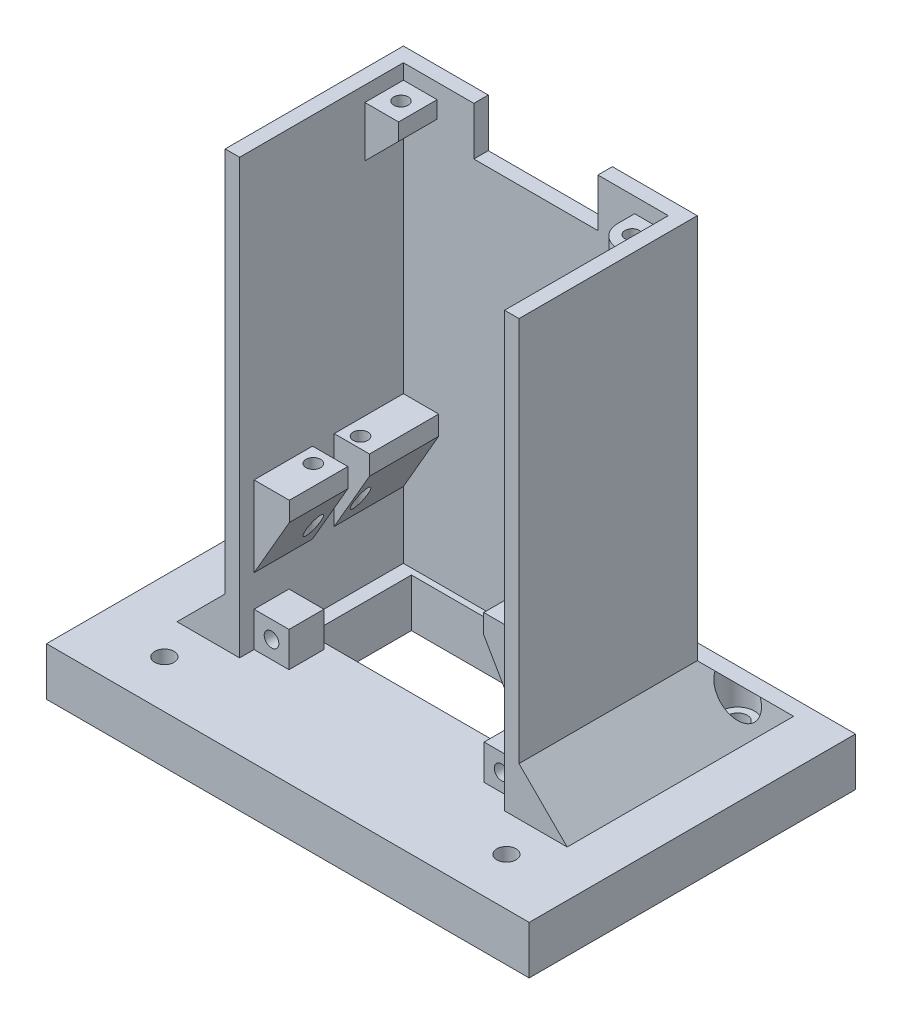
SolidWorks part; units mm, degrees
ref_plane "Front" through (0, 0, 0) normal (0, 0, 1) x (1, 0, 0)
ref_plane "Top" through (0, 0, 0) normal (0, 1, 0) x (1, 0, 0)
ref_plane "Right" through (0, 0, 0) normal (1, 0, 0) x (0, 0, -1)
sketch "Sketch1" plane through (0, 0, 0) normal (0, 0, 1) x (1, 0, 0)
  line L1 (0, 0) -> (55, 0)
  line L2 (0, 0) -> (0, 80)
  line L3 (0, 80) -> (55, 80)
  line L4 (55, 0) -> (55, 80)
  dimension "D1" = 55
  dimension "D2" = 80
extrude "BackPanel" add sketch "Sketch1" along normal blind 3
sketch "Sketch2" plane through (0, 0, 3) normal (0, 0, 1) x (1, 0, 0)
  line L0 (0, 80) -> (0, 0) construction
  line L1 (0, 16.5) -> (7.325, 16.5)
  line L2 (0, 16.5) -> (0, 20.5)
  line L3 (0, 20.5) -> (7.325, 20.5)
  line L4 (7.325, 16.5) -> (7.325, 20.5)
  line L5 (55, 0) -> (55, 80) construction
  line L6 (55, 16.5) -> (47.675, 16.5)
  line L7 (55, 16.5) -> (55, 20.5)
  line L8 (55, 20.5) -> (47.675, 20.5)
  line L9 (47.675, 16.5) -> (47.675, 20.5)
  line L10 (7.325, 16.5) -> (47.675, 16.5) construction
  line L11 (0, 0) -> (55, 0) construction
  dimension "D1" = 40.35
  dimension "D2" = 20.5
  dimension "D3" = 4
extrude "MotorMount" add sketch "Sketch2" along normal blind 34
sketch "Sketch3" plane through (0, 0, 0) normal (-1, 0, 0) x (0, 0, 1)
  line L0 (37, 20.5) -> (37, 16.5) construction
  line L1 (0, 0) -> (37, 0)
  line L2 (0, 0) -> (0, 80)
  line L3 (0, 80) -> (37, 80)
  line L4 (37, 0) -> (37, 80)
  line L5 (3, 80) -> (0, 80) construction
  point P7 (0, 80)
extrude "SidePanel2" add sketch "Sketch3" along normal blind 3
sketch "Sketch4" plane through (55, 0, 0) normal (1, 0, 0) x (0, 0, -1)
  line L0 (-37, 16.5) -> (-37, 20.5) construction
  line L1 (0, 80) -> (-37, 80)
  line L2 (0, 80) -> (0, 0)
  line L3 (0, 0) -> (-37, 0)
  line L4 (-37, 80) -> (-37, 0)
extrude "SidePanel1" add sketch "Sketch4" along normal blind 3
sketch "Sketch6" plane through (0, 0, 37) normal (0, 0, 1) x (1, 0, 0)
  line L0 (7.325, 16.5) -> (0, 3.8127)
  line L1 (0, 0) -> (0, 16.5) construction
  line L2 (0, 3.8127) -> (0, 16.5)
  line L3 (0, 16.5) -> (7.325, 16.5)
  line L4 (47.675, 16.5) -> (55, 16.5)
  line L5 (55, 16.5) -> (55, 3.8127)
  line L6 (55, 16.5) -> (55, 0) construction
  line L7 (55, 3.8127) -> (47.675, 16.5)
  line L8 (0, 16.5) -> (0, 0) construction
  dimension "D1" = 150
extrude "MotorSupportAngles" add sketch "Sketch6" against normal up to surface (34 mm away) up to face at (27.5, 25.6667, 3)
sketch "Sketch5" plane through (0, 20.5, 0) normal (0, 1, 0) x (1, 0, 0)
  line L0 (3.2, -3) -> (3.2, -15.1) construction
  line L2 (7.325, -3) -> (0, -3) construction
  line L3 (3.2, -24.9) -> (3.2, -37) construction
  line L4 (7.325, -37) -> (0, -37) construction
  line L5 (0, -3) -> (55, -3) construction
  line L6 (27.5, -3) -> (27.5, -15.1) construction
  line L7 (3.2, -15.1) -> (51.8, -15.1) construction
  circle A0 centre (3.2, -15.1) radius 1.515
  circle A1 centre (3.2, -24.9) radius 1.515
  circle A2 centre (51.8, -15.1) radius 1.515
  circle A3 centre (51.8, -24.9) radius 1.515
  dimension "D3" = 3.03
  dimension "D1" = 9.8
  dimension "D2" = 48.6
extrude "MotorHolesSet1" cut sketch "Sketch5" against normal up to surface (11.1447 mm away) contours A0 | A1 region at (3.2, 20.5, 15.1) region at (3.2, 20.5, 24.9) up to face at (3.6625, 10.1564, 20)
extrude "MotorHolesSet2" cut sketch "Sketch5<3>" against normal up to surface (11.1447 mm away) contours A2 | A3 region at (51.8, 20.5, 15.1) region at (51.8, 20.5, 24.9) up to face at (51.3375, 10.1564, 20)
sketch "Sketch5<3>" plane through (0, 20.5, 0) normal (0, 1, 0) x (1, 0, 0) same geometry as "Sketch5"
sketch "Sketch7" plane through (0, 0, 0) normal (0, -1, 0) x (1, 0, 0)
  line L1 (-3, 0) -> (58, 0)
  line L2 (-3, 0) -> (-3, 37)
  line L3 (-3, 37) -> (58, 37)
  line L4 (58, 0) -> (58, 37)
extrude "BottomPlate" add sketch "Sketch7" along normal blind 3
sketch "Sketch8" plane through (0, 0, 37) normal (0, 0, 1) x (1, 0, 0)
  line L0 (58, 80) -> (58, -3) construction
  line L1 (-3, -3) -> (58, -3)
  line L2 (-3, -3) -> (-3, 0)
  line L3 (-3, 0) -> (58, 0)
  line L4 (58, -3) -> (58, 0)
extrude "Cut-Extrude1" cut sketch "Sketch8" against normal up to surface (37 mm away) up to face at (27.5, 38.5, 0)
sketch "Sketch9" plane through (0, 0, 37) normal (0, 0, 1) x (1, 0, 0)
  line L1 (-3, 0) -> (-8.75, 0)
  line L2 (-3, 0) -> (-3, 4)
  line L3 (-3, 4) -> (-8.75, 4)
  line L4 (-8.75, 0) -> (-8.75, 4)
  line L5 (58, 0) -> (63.75, 0)
  line L6 (58, 0) -> (58, 4)
  line L7 (58, 4) -> (63.75, 4)
  line L8 (63.75, 0) -> (63.75, 4)
  dimension "D1" = 72.5
  dimension "D2" = 4
extrude "Boss-Extrude1" [suppressed] add sketch "Sketch9" against normal up to surface (37 mm away)
sketch "Sketch10" [suppressed] plane through (0, 0, 37) normal (0, 0, 1) x (1, 0, 0)
  line L1 (-8.75, 4) -> (-12.75, 4)
  line L2 (-8.75, 4) -> (-8.75, -32.7637)
  line L3 (-8.75, -32.7637) -> (-12.75, -32.7637)
  line L4 (-12.75, 4) -> (-12.75, -32.7637)
  line L5 (63.75, 4) -> (67.75, 4)
  line L6 (63.75, 4) -> (63.75, -32.7637)
  line L7 (63.75, -32.7637) -> (67.75, -32.7637)
  line L8 (67.75, 4) -> (67.75, -32.7637)
  dimension "D1" = 4
extrude "Boss-Extrude2" [suppressed] add sketch "Sketch10" against normal up to surface (37 mm away)
sketch "Sketch11" [suppressed] plane through (0, 0, 37) normal (0, 0, 1) x (1, 0, 0)
  line L0 (-12.75, 4) -> (-3, 13.75)
  line L1 (-3, 4) -> (-3, 70) construction
  line L2 (-3, 13.75) -> (-3, 4)
  line L3 (-3, 4) -> (-12.75, 4)
  line L4 (67.75, 4) -> (58, 4)
  line L5 (58, 4) -> (58, 13.75)
  line L6 (58, 70) -> (58, 4) construction
  line L7 (58, 13.75) -> (67.75, 4)
extrude "Boss-Extrude3" [suppressed] add sketch "Sketch11" against normal up to surface (37 mm away)
sketch "Sketch12" [suppressed] plane through (-12.75, 0, 0) normal (1, 0, 0) x (0, 0, -1)
  line L0 (-18.5, -32.7637) -> (-18.5, -23.4813) construction
  line L1 (0, -32.7637) -> (-37, -32.7637) construction
  line L2 (-37, -32.7637) -> (-37, 0) construction
  line L3 (0, -32.7637) -> (0, 0) construction
  line L4 (0, -32.7637) -> (-37, -32.7637) construction
  line L5 (-37, -14.9767) -> (-37, -32.7637)
  line L6 (-37, -32.7637) -> (0, -32.7637)
  line L7 (0, -32.7637) -> (0, -14.9767)
  arc A0 (-37, -14.9767) -> (0, -14.9767) centre (-18.5, -14.2494) ccw
  line M15 (0, 4) -> (0, -32.7637)
  line M16 (0, -32.7637) -> (-37, -32.7637)
  line M17 (-37, -32.7637) -> (-37, 4)
extrude "Cut-Extrude3" [suppressed] cut sketch "Sketch12" along normal up to surface (80.5 mm away) contours A0 M16 M15 | A0 L6 M17
sketch "Sketch13" [suppressed] plane through (-12.75, 0, 0) normal (-1, 0, 0) x (0, 0, 1)
  circle A0 centre (18.5, -24.2494) radius 2.4315
  arc A1 (0, -14.9767) -> (37, -14.9767) centre (18.5, -14.2494) ccw construction
  dimension "D1" = 10
extrude "Cut-Extrude4" [suppressed] cut sketch "Sketch13" against normal up to surface (4 mm away)
sketch "Sketch14" plane through (0, 0, 37) normal (0, 0, 1) x (1, 0, 0)
  line L1 (0, 20.5) -> (-3, 20.5)
  line L2 (0, 20.5) -> (0, 80)
  line L3 (0, 80) -> (-3, 80)
  line L4 (-3, 20.5) -> (-3, 80)
extrude "Cut-Extrude5" [suppressed] cut sketch "Sketch14" against normal up to surface (34 mm away)
sketch "Sketch15" plane through (0, 0, 37) normal (0, 0, 1) x (1, 0, 0)
  line L1 (-3, 0) -> (58, 0)
  line L2 (-3, 0) -> (-3, 80)
  line L3 (-3, 80) -> (58, 80)
  line L4 (58, 0) -> (58, 80)
extrude "Boss-Extrude4" [suppressed] add sketch "Sketch15" along normal blind 3
ref_axis "Axis1" [suppressed] through (51.8, 13.7312, 15.1) along (0, 1, 0)
ref_axis "Axis2" [suppressed] through (51.8, 13.7312, 24.9) along (0, 1, 0)
ref_plane "Plane2" [suppressed] through (51.8, 0, 0) normal (-1, 0, 0) x (0, 0, 1)
ref_plane "Plane3" [suppressed] through (37.65, 0, 0) normal (-1, 0, 0) x (0, 0, 1)
ref_plane "Plane4" [suppressed] through (0, 0, 20) normal (0, 0, -1) x (-1, 0, 0)
sketch "Sketch16" [suppressed] plane through (37.65, 0, 0) normal (-1, 0, 0) x (0, 0, 1)
  line L0 (0, 19.0475) -> (-19.25, 5.599)
  line L1 (0, 70) -> (0, 0) construction
  line L3 (0, 0) -> (0, 19.0475)
  line L4 (40, 0) -> (40, 19.0475)
  line L5 (40, 70) -> (40, 0) construction
  line L6 (40, 19.0475) -> (59.25, 5.599)
  line L8 (-19.25, 5.599) -> (-9.625, 12.3233)
  line L9 (-19.25, 0) -> (0, 0)
  line L10 (-19.25, 5.599) -> (-19.25, 0)
  line L11 (40, 0) -> (59.25, 0)
  line L12 (59.25, 0) -> (59.25, 5.599)
  dimension "D1" = 78.5
extrude "Boss-Extrude5" [suppressed] add sketch "Sketch16" along normal blind 15 and the other way blind 15 contours L0 L10 L9 L3 | L11 L12 L6 L4
ref_plane "Plane5" [suppressed] through (0, 0, -19.25) normal (0, 0, -1) x (-1, 0, 0)
sketch "Sketch18" [suppressed] plane through (0, 0, -19.25) normal (0, 0, -1) x (-1, 0, 0)
  line L0 (-37.65, 0) -> (-37.65, -23.5) construction
  line L2 (-22.65, 0) -> (-22.65, -23.5)
  line L3 (-52.65, 0) -> (-52.65, -23.5)
  line L4 (-52.65, 0) -> (-22.65, 0)
  line L5 (-52.65, 0) -> (-37.65, 0) construction
  line L6 (-52.65, 0) -> (-22.65, 0) construction
  arc A0 (-22.65, 0) -> (-52.65, 0) centre (-37.65, 0) ccw
  arc A1 (-52.65, -23.5) -> (-22.65, -23.5) centre (-37.65, -23.5) ccw
  circle A2 centre (-37.65, -23.5) radius 2
  point P4 (-37.65, -11.75)
  point P9 (-22.65, 0)
  dimension "D1" = 4
  dimension "D2" = 23.5
extrude "Boss-Extrude6" [suppressed] add sketch "Sketch18" against normal blind 3 contours L3 A1 L2 L4
ref_plane "Plane6" [suppressed] through (0, 0, 59.25) normal (0, 0, 1) x (1, 0, 0)
sketch "Sketch19" [suppressed] plane through (0, 0, 59.25) normal (0, 0, 1) x (1, 0, 0)
  line L0 (37.65, 0) -> (37.65, -23.5) construction
  line L1 (52.65, 0) -> (22.65, 0) construction
  line L2 (52.65, 0) -> (52.65, -23.5)
  line L3 (22.65, 0) -> (22.65, -23.5)
  line L4 (52.65, 0) -> (52.65, -23.5) construction
  line L5 (22.65, 0) -> (52.65, 0)
  arc A0 (52.65, 0) -> (22.65, 0) centre (37.65, 0) ccw
  arc A1 (22.65, -23.5) -> (52.65, -23.5) centre (37.65, -23.5) ccw
  circle A2 centre (37.65, -23.5) radius 2
  point P0 (37.65, -23.5)
  point P6 (37.65, -11.75)
  dimension "D1" = 4
extrude "Boss-Extrude7" [suppressed] add sketch "Sketch19" against normal blind 3 contours L3 A1 L2 L5
fillet "Fillet1" [suppressed] radius 4
fillet "Fillet2" [suppressed] radius 4
ref_plane "Plane7" through (0, -30, 0) normal (0, -1, 0) x (-1, 0, 0)
sketch "Sketch20" plane through (0, -30, 0) normal (0, -1, 0) x (-1, 0, 0)
  line L0 (3, -37) -> (3, -41.2394) construction
  line L1 (3, -41.2394) -> (-58, -41.2394) construction
  line L2 (-58, -41.2394) -> (-58, -37) construction
  line L3 (3, -41.2394) -> (-58, 0) construction
  line L4 (-58, 0) -> (3, 0) construction
  line L5 (3, 0) -> (-58, -41.2394) construction
  line L7 (8, 3.3803) -> (-63, 3.3803)
  line L8 (8, 3.3803) -> (8, -44.6197)
  line L9 (8, -44.6197) -> (-63, -44.6197)
  line L10 (-63, 3.3803) -> (-63, -44.6197)
  line L11 (8, 3.3803) -> (-63, -44.6197) construction
  line L12 (8, -44.6197) -> (-63, 3.3803) construction
  line L13 (-77.5981, 13.2494) -> (22.5981, 13.2494)
  line L14 (-77.5981, 13.2494) -> (-77.5981, -54.4888)
  line L15 (-77.5981, -54.4888) -> (22.5981, -54.4888)
  line L16 (22.5981, 13.2494) -> (22.5981, -54.4888)
  line L17 (-77.5981, 13.2494) -> (22.5981, -54.4888) construction
  line L18 (-77.5981, -54.4888) -> (22.5981, 13.2494) construction
  circle A0 centre (8, -44.6197) radius 2
  circle A1 centre (-63, -44.6197) radius 2
  circle A2 centre (-63, 3.3803) radius 2
  circle A3 centre (8, 3.3803) radius 2
  point P6 (-27.5, -20.6197)
  point P19 (-27.5, -20.6197)
  point P20 (6.3431, -43.4996)
  point P25 (9.6569, -45.7399)
  dimension "D2" = 4
  dimension "D1" = 71
  dimension "D3" = 48
extrude "Boss-Extrude8" add sketch "Sketch20" against normal blind 20 separate body contours A3 L7 A2 L10 A1 L9 A0 L8 | L16 L13 L14 L15 A3 L8 A0 L9 A1 L10 A2 L7 region at (27.5, -30, 20.6197) region at (27.5, -30, -12.04)
sketch "Sketch21" plane through (0, 0, 0) normal (0, -1, 0) x (1, 0, 0)
  line L0 (58, 0) -> (58, 37) construction
  line L1 (-3, 0) -> (58, 0)
  line L2 (-3, 0) -> (-3, 37)
  line L3 (-3, 37) -> (0, 37)
  line L4 (58, 0) -> (58, 37)
  line L5 (55, 37) -> (58, 37)
  line L6 (0, 3) -> (55, 3)
  line L7 (0, 3) -> (0, 37)
  line L9 (55, 3) -> (55, 37)
extrude "Boss-Extrude10" add sketch "Sketch21" along normal up to surface (10 mm away) up to face at (63, -10, -5.3803)
sketch "Sketch22" plane through (0, 0, 3) normal (0, 0, 1) x (1, 0, 0)
  line L0 (0, 76.85) -> (7, 76.85)
  line L1 (55, 80) -> (0, 80) construction
  line L2 (7, 76.85) -> (7, 73.35)
  line L4 (55, 76.85) -> (55, 66.35)
  line L6 (55, 76.85) -> (48, 76.85)
  line L7 (48, 76.85) -> (48, 73.35)
  line L11 (0, 76.85) -> (0, 66.35)
  line L12 (0, 80) -> (0, 20.5) construction
  line L13 (0, 66.35) -> (7, 73.35)
  line L14 (0, 20.5) -> (0, 80) construction
  line L16 (55, 66.35) -> (48, 73.35)
  dimension "D1" = 7
  dimension "D2" = 3.5
  dimension "D3" = 45
  dimension "D4" = 3.15
  dimension "3.15" = 3.15
extrude "Boss-Extrude11" add sketch "Sketch22" along normal blind 8
sketch "Sketch24" plane through (0, 76.85, 0) normal (0, 1, 0) x (1, 0, 0)
  line L0 (0, -3) -> (7, -11) construction
  line L1 (7, -11) -> (7, -3) construction
  line L2 (7, -3) -> (0, -11) construction
  line L3 (48, -11) -> (55, -3) construction
  line L4 (55, -3) -> (48, -3) construction
  line L5 (48, -3) -> (55, -11) construction
  circle A0 centre (3.5, -7) radius 1.505
  circle A1 centre (51.5, -7) radius 1.505
  dimension "D1" = 3.01
extrude "Cut-Extrude6" cut sketch "Sketch24" against normal blind 4
ref_plane "Plane8" through (55, 80, 3) normal (-1, 0, 0) x (0, 0, 1)
sketch "Sketch25" plane through (0, -10, 0) normal (0, 1, 0) x (1, 0, 0)
  line L0 (0, -3) -> (0, -37) construction
  line L1 (0, -34) -> (7.25, -34)
  line L2 (0, -34) -> (0, -26.75)
  line L3 (0, -26.75) -> (7.25, -26.75)
  line L4 (7.25, -34) -> (7.25, -26.75)
  line L5 (55, -34) -> (47.75, -34)
  line L6 (55, -34) -> (55, -26.75)
  line L7 (55, -26.75) -> (47.75, -26.75)
  line L8 (47.75, -34) -> (47.75, -26.75)
  line L9 (55, -37) -> (55, -3) construction
  dimension "D1" = 3
  dimension "D2" = 7.25
  dimension "D3" = 3
extrude "Boss-Extrude12" add sketch "Sketch25" along normal blind 7.25
sketch "Sketch26" plane through (0, 0, 34) normal (0, 0, 1) x (1, 0, 0)
  line L0 (0, -2.75) -> (7.25, -10) construction
  line L1 (7.25, -10) -> (7.25, -2.75) construction
  line L2 (7.25, -2.75) -> (0, -10) construction
  line L3 (55, -2.75) -> (47.75, -10) construction
  line L4 (47.75, -10) -> (47.75, -2.75) construction
  line L5 (47.75, -2.75) -> (55, -10) construction
  line L6 (47.75, -10) -> (55, -10) construction
  line L7 (55, -2.75) -> (55, -10) construction
  circle A0 centre (3.625, -6.375) radius 1.515
  circle A1 centre (51.375, -6.375) radius 1.515
  dimension "D1" = 3.03
extrude "Cut-Extrude7" cut sketch "Sketch26" against normal up to surface (7.25 mm away) up to face at (3.625, -6.375, 26.75)
sketch "Sketch27" plane through (0, 20.5, 0) normal (0, 1, 0) x (1, 0, 0)
  line L0 (0, -21.8612) -> (7.325, -21.8612)
  line L1 (0, -37) -> (0, -3) construction
  line L2 (7.325, -37) -> (7.325, -3) construction
  line L3 (7.325, -21.8612) -> (7.325, -17.361)
  line L4 (7.325, -17.361) -> (0, -17.361)
  line L5 (0, -17.361) -> (0, -21.8612)
extrude "Cut-Extrude8" cut sketch "Sketch27" against normal up to surface (4 mm away) up to face at (4.715, 11.9793, 15.1)
fillet "Fillet3" radius 4.5 1 edges at (48, 75.1, 11)
sketch "Sketch28" plane through (0, 0, 37) normal (0, 0, 1) x (1, 0, 0)
  line L1 (0, 3.8127) -> (55, 3.8127)
  line L2 (0, 3.8127) -> (0, 20.5)
  line L3 (0, 20.5) -> (55, 20.5)
  line L4 (55, 3.8127) -> (55, 20.5)
extrude "Cut-Extrude9" cut sketch "Sketch28" against normal blind 3
sketch "Sketch30" plane through (0, -30, 0) normal (0, -1, 0) x (1, 0, 0)
  line L1 (77.5981, -13.2494) -> (-22.5981, -13.2494)
  line L2 (77.5981, -13.2494) -> (77.5981, 54.4888)
  line L3 (77.5981, 54.4888) -> (-22.5981, 54.4888)
  line L4 (-22.5981, -13.2494) -> (-22.5981, 54.4888)
extrude "Cut-Extrude10" cut sketch "Sketch30" against normal blind 10
chamfer "Chamfer1" distance 10 angle 45 1 edges at (-3, -10, 18.5)
chamfer "Chamfer2" distance 10 angle 45 1 edges at (58, -10, 18.5)
chamfer "Chamfer3" distance 10 angle 45 1 edges at (27.5, -10, 0)
sketch "Sketch31" plane through (0, -10, 0) normal (0, 1, 0) x (1, 0, 0)
  circle A0 centre (63, 3.3803) radius 3.5
  circle A1 centre (-8, 3.3803) radius 3.5
  dimension "D1" = 7
extrude "Cut-Extrude11" cut sketch "Sketch31" along normal blind 10
sketch "Sketch32" plane through (0, -10, 0) normal (0, 1, 0) x (1, 0, 0)
  line L0 (0, -26.75) -> (2.9286, -25.4854)
  line L1 (2.9286, -25.4854) -> (52.0714, -25.4854)
  line L2 (2.9286, -25.4854) -> (2.9286, -4.2646)
  line L3 (2.9286, -4.2646) -> (52.0714, -4.2646)
  line L4 (52.0714, -25.4854) -> (52.0714, -4.2646)
  line L5 (52.0714, -4.2646) -> (55, -3)
extrude "Cut-Extrude12" cut sketch "Sketch32" against normal up to surface (10 mm away) contours L1 L4 L3 L2 region at (27.5, -10, 14.875) up to face at (27.5, -20, 20.6197)
sketch "Sketch33" plane through (0, 80, 0) normal (0, 1, 0) x (1, 0, 0)
  line L0 (55, -3) -> (0, -3) construction
  line L1 (14.6223, -3) -> (40.3777, -3)
  line L2 (14.6223, -3) -> (14.6223, 0)
  line L3 (14.6223, 0) -> (40.3777, 0)
  line L4 (40.3777, -3) -> (40.3777, 0)
  line L5 (58, 0) -> (-3, 0) construction
  line L6 (-3, 0) -> (14.6223, 0) construction
  line L7 (40.3777, 0) -> (58, 0) construction
extrude "Cut-Extrude13" cut sketch "Sketch33" against normal blind 10
